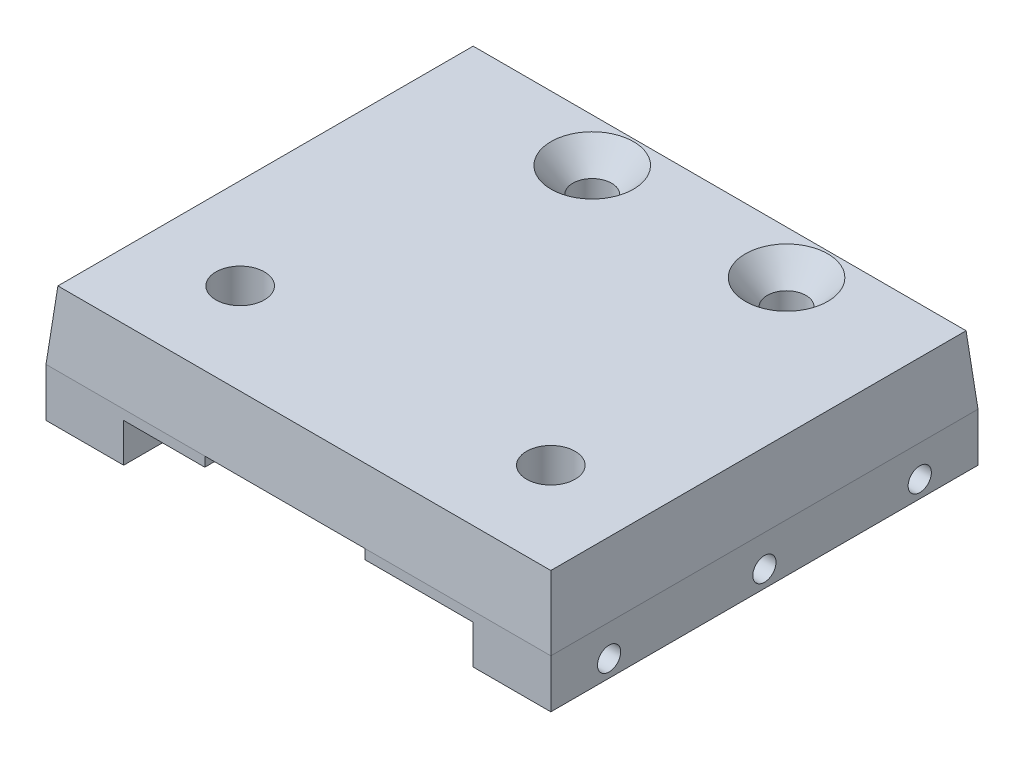
SolidWorks part; units mm, degrees
material "6061 Alloy"
ref_plane "Front Plane" through (0, 0, 0) normal (0, 0, 1) x (1, 0, 0)
ref_plane "Top Plane" through (0, 0, 0) normal (0, 1, 0) x (1, 0, 0)
ref_plane "Right Plane" through (0, 0, 0) normal (1, 0, 0) x (0, 0, -1)
sketch "Sketch1" plane through (0, 0, 0) normal (0, 1, 0) x (1, 0, 0)
  line L1 (41.275, -34.925) -> (-41.275, -34.925)
  line L2 (41.275, -34.925) -> (41.275, 34.925)
  line L3 (41.275, 34.925) -> (-41.275, 34.925)
  line L4 (-41.275, -34.925) -> (-41.275, 34.925)
  line L5 (41.275, -34.925) -> (-41.275, 34.925) construction
  line L6 (41.275, 34.925) -> (-41.275, -34.925) construction
  line L7 (-22.225, 34.925) -> (28.575, 34.925)
  line L8 (-22.225, 34.925) -> (-22.225, 92.075)
  line L9 (-22.225, 92.075) -> (28.575, 92.075)
  line L10 (28.575, 34.925) -> (28.575, 92.075)
  point P0 (0, 0)
  dimension "D1" = 82.55
  dimension "D2" = 69.85
  dimension "D3" = 12.7
  dimension "D4" = 19.05
  dimension "D5" = 50.8
  dimension "D6" = 127
extrude "Boss-Extrude1" add sketch "Sketch1" along normal blind 7.9375 contours L4 L1 L2 L3 region at (0, 0, 0)
sketch "Sketch2" plane through (0, 7.9375, 0) normal (0, 1, 0) x (1, 0, 0)
  line L1 (-41.275, -34.925) -> (41.275, -34.925)
  line L2 (-41.275, -34.925) -> (-41.275, 34.925)
  line L3 (-41.275, 34.925) -> (41.275, 34.925)
  line L4 (41.275, -34.925) -> (41.275, 34.925)
extrude "Boss-Extrude2" add sketch "Sketch2" along normal blind 3.175
hole_wizard "3/8-16 Tapped Hole1" positions "Sketch10" profile "Sketch11" tap size "3/8-16" standard "ANSI Inch"
sketch "Sketch10" plane through (0, 11.1125, 0) normal (0, 1, 0) x (1, 0, 0)
  line L0 (-41.275, 34.925) -> (-41.275, -34.925) construction
  line L1 (-41.275, -34.925) -> (41.275, -34.925) construction
  line L2 (41.275, -34.925) -> (41.275, 34.925) construction
  point P0 (-25.4, -19.05)
  point P2 (25.4, -19.05)
  dimension "D1" = 15.875
  dimension "D2" = 15.875
  dimension "D3" = 15.875
  dimension "D4" = 15.875
sketch "Sketch11" plane through (-25.4, 11.1125, 19.05) normal (1, 0, 0) x (0, 0, 1)
  line L0 (0, 0) -> (0, 11.9097)
  line L1 (0, 11.9097) -> (3.9687, 9.525)
  line L2 (3.9687, 9.525) -> (3.9687, 0)
  line L5 (3.9687, 0) -> (0, 0)
  line L10 (0, 11.9097) -> (-3.9688, 9.525) construction
  line L11 (0, -6.35) -> (0, 107.95) construction
  dimension "Tap Drill Dia." = 7.9375
  dimension "Tap Drill Depth" = 9.525
  dimension "Drill Angle" = 118
cosmetic thread "Hole Thread4" parameters "D1"=19.05, "D2"=9.525
cosmetic thread "Hole Thread5" parameters "D1"=19.05, "D2"=9.525
draft "Draft1" type of draft neutral plane draft angle 5 neutral plane "Top Plane" faces to draft 4 face at (0, 5.5563, -34.925) face at (-41.275, 5.5563, 0) face at (0, 5.5563, 34.925) face at (41.275, 5.5563, 0) neutral plane through (0, 0, 0) neutral plane normal (0, 1, 0) parameters "D1"=5
sketch "Sketch3" plane through (0, 0, 0) normal (0, -1, 0) x (1, 0, 0)
  line L7 (41.275, 34.925) -> (28.575, 34.925)
  line L8 (41.275, 34.925) -> (41.275, -34.925)
  line L9 (41.275, -34.925) -> (28.575, -34.925)
  line L10 (28.575, 34.925) -> (28.575, -34.925)
  line L13 (-41.275, -34.925) -> (-28.575, -34.925)
  line L14 (-41.275, -34.925) -> (-41.275, 34.925)
  line L15 (-41.275, 34.925) -> (-28.575, 34.925)
  line L16 (-28.575, -34.925) -> (-28.575, 34.925)
  dimension "D1" = 12.7
  dimension "D2" = 12.7
extrude "Boss-Extrude3" add sketch "Sketch3" along normal blind 7.9375
sketch "Sketch4" plane through (0, 0, 0) normal (0, -1, 0) x (1, 0, 0)
  line L1 (-28.575, 34.925) -> (-15.3077, 34.925)
  line L2 (-28.575, 34.925) -> (-28.575, -34.925)
  line L3 (-28.575, -34.925) -> (-15.3077, -34.925)
  line L4 (-15.3077, 34.925) -> (-15.3077, -34.925)
  line L6 (28.575, 34.925) -> (10.8909, 34.925)
  line L7 (28.575, 34.925) -> (28.575, -34.925)
  line L8 (28.575, -34.925) -> (10.8909, -34.925)
  line L9 (10.8909, 34.925) -> (10.8909, -34.925)
extrude "Wear Pads" add sketch "Sketch4" along normal blind 1.5875
hole_wizard "#10-24 Tapped Hole1" positions "Sketch5" profile "Sketch6" tap size "#10-24" standard "ANSI Inch" end condition up to next
sketch "Sketch5" plane through (41.275, 0, 0) normal (1, 0, 0) x (0, 0, -1)
  line L6 (-34.925, -5.1516) -> (34.925, -5.1516) construction
  line L8 (-34.925, -7.9375) -> (-34.925, 0) construction
  line L9 (34.925, -7.9375) -> (34.925, 0) construction
  point P0 (-25.4, -5.1516)
  point P2 (25.4, -5.1516)
  point P29 (0, -5.1516)
  dimension "D1" = 9.525
  dimension "D2" = 9.525
sketch "Sketch6" plane through (41.275, -5.1516, 25.4) normal (0, 1, 0) x (0, 0, -1)
  line L0 (0, 0) -> (0, 12.7)
  line L1 (0, 12.7) -> (1.8986, 12.7)
  line L2 (1.8986, 12.7) -> (1.8986, 0)
  line L5 (1.8986, 0) -> (0, 0)
  line L11 (0, -6.35) -> (0, 107.95) construction
  dimension "Thru Tap Drill Dia." = 3.7973
  dimension "Thru Tap Drill Depth" = 12.7
cosmetic thread "Hole Thread1" parameters "D2"=4.826
cosmetic thread "Hole Thread2" parameters "D2"=4.826
cosmetic thread "Hole Thread3" parameters "D2"=4.826
hole_wizard "1/4 (0.25) Diameter Hole1" positions "Sketch16" profile "Sketch17" hole size "1/4" standard "ANSI Inch"
sketch "Sketch16" plane through (0, 11.1125, 0) normal (0, 1, 0) x (1, 0, 0)
  point P0 (-13.6771, 26.7977)
  point P13 (18.1019, 26.7977)
  point P16 (-13.6771, 26.7977)
  point P17 (0, 0)
  point P18 (18.1019, 26.7977)
sketch "Sketch17" plane through (-13.6771, 11.1125, -26.7977) normal (1, 0, 0) x (0, 0, 1)
  line L0 (0, 0) -> (0, 10.7977)
  line L1 (0, 10.7977) -> (3.175, 8.89)
  line L2 (3.175, 8.89) -> (3.175, 4.1053)
  line L3 (3.175, 4.1053) -> (6.7437, 0)
  line L5 (6.7437, 0) -> (0, 0)
  line L6 (-3.175, 4.1053) -> (-6.7437, 0) construction
  line L10 (0, 10.7977) -> (-3.175, 8.89) construction
  line L11 (0, -6.35) -> (0, 107.95) construction
  dimension "Hole Dia." = 6.35
  dimension "Hole Depth" = 8.89
  dimension "Near C'Sink Dia." = 13.4874
  dimension "Near C'Sink Angle" = 82
  dimension "Drill Angle" = 118
hole_wizard "1/4-20 Tapped Hole1" positions "Sketch18" profile "Sketch19" tap size "1/4-20" standard "ANSI Inch"
sketch "Sketch18" plane through (0, -7.9375, 0) normal (0, -1, 0) x (-1, 0, 0)
  point P0 (-33.3375, 15.875)
  point P3 (-33.3375, -15.875)
sketch "Sketch19" plane through (33.3375, -7.9375, -15.875) normal (1, 0, 0) x (0, 0, -1)
  line L0 (0, 0) -> (0, 12.9638)
  line L1 (0, 12.9638) -> (2.5527, 11.43)
  line L2 (2.5527, 11.43) -> (2.5527, 0)
  line L5 (2.5527, 0) -> (0, 0)
  line L10 (0, 12.9638) -> (-2.5527, 11.43) construction
  line L11 (0, -6.35) -> (0, 107.95) construction
  dimension "Tap Drill Dia." = 5.1054
  dimension "Tap Drill Depth" = 11.43
  dimension "Drill Angle" = 118
cosmetic thread "Hole Thread6" parameters "D1"=12.7, "D2"=6.35
cosmetic thread "Hole Thread7" parameters "D1"=12.7, "D2"=6.35
hole_wizard "1/4-20 Tapped Hole2" positions "Sketch20" profile "Sketch21" tap size "1/4-20" standard "ANSI Inch"
sketch "Sketch20" plane through (0, -7.9375, 0) normal (0, -1, 0) x (-1, 0, 0)
  point P0 (33.3375, -15.875)
  point P3 (33.3375, 15.875)
sketch "Sketch21" plane through (-33.3375, -7.9375, 15.875) normal (1, 0, 0) x (0, 0, -1)
  line L0 (0, 0) -> (0, 12.9638)
  line L1 (0, 12.9638) -> (2.5527, 11.43)
  line L2 (2.5527, 11.43) -> (2.5527, 0)
  line L5 (2.5527, 0) -> (0, 0)
  line L10 (0, 12.9638) -> (-2.5527, 11.43) construction
  line L11 (0, -6.35) -> (0, 107.95) construction
  dimension "Tap Drill Dia." = 5.1054
  dimension "Tap Drill Depth" = 11.43
  dimension "Drill Angle" = 118
cosmetic thread "Hole Thread8" parameters "D1"=12.7, "D2"=6.35
cosmetic thread "Hole Thread9" parameters "D1"=12.7, "D2"=6.35
